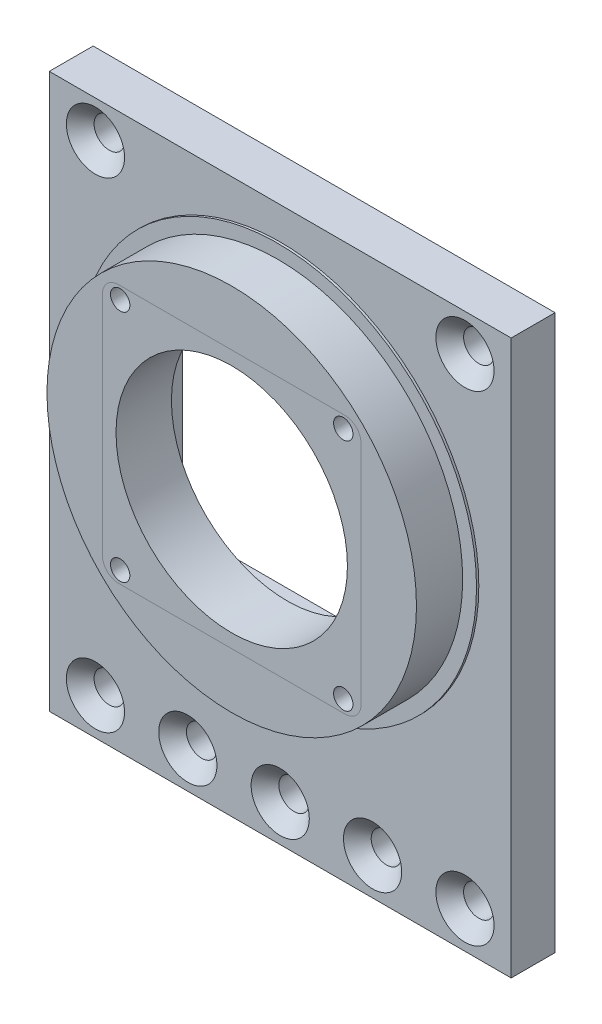
SolidWorks part; units mm, degrees
material "PVC rigide"
ref_plane "Plan de face" through (0, 0, 0) normal (0, 0, 1) x (1, 0, 0)
ref_plane "Plan de dessus" through (0, 0, 0) normal (0, 1, 0) x (1, 0, 0)
ref_plane "Plan de droite" through (0, 0, 0) normal (1, 0, 0) x (0, 0, -1)
sketch "Esquisse1" plane through (0, 0, 0) normal (0, 0, 1) x (1, 0, 0)
  line L1 (28, 28) -> (-28, 28)
  line L2 (28, 28) -> (28, -28)
  line L3 (28, -28) -> (-28, -28)
  line L4 (-28, 28) -> (-28, -28)
  line L5 (28, 28) -> (-28, -28) construction
  line L6 (28, -28) -> (-28, 28) construction
  line L7 (50, 50) -> (-50, 50)
  line L8 (50, 50) -> (50, -50)
  line L9 (50, -50) -> (-50, -50)
  line L10 (-50, 50) -> (-50, -50)
  line L11 (50, 50) -> (-50, -50) construction
  line L12 (50, -50) -> (-50, 50) construction
  circle A0 centre (0, 0) radius 40 construction
  point P0 (0, 0)
  dimension "D2" = 80
  dimension "D1" = 56
  dimension "D3" = 100
extrude "Boss.-Extru.1" add sketch "Esquisse1" along normal blind 10
fillet "Congé1" radius 3.5 4 edges at (-28, -28, 5) (28, 28, 5) (-28, 28, 5) (28, -28, 5)
sketch "Esquisse3" plane through (0, 0, 10) normal (0, 0, 1) x (1, 0, 0)
  line L5 (-28, 24.5) -> (-28, -24.5)
  line L6 (24.5, 28) -> (-24.5, 28)
  line L7 (28, -24.5) -> (28, 24.5)
  line L8 (-24.5, -28) -> (24.5, -28)
  line L9 (-28, 24.5) -> (-28, -24.5)
  line L10 (24.5, 28) -> (-24.5, 28)
  line L11 (28, -24.5) -> (28, 24.5)
  line L12 (-24.5, -28) -> (24.5, -28)
  circle A0 centre (0, 0) radius 40
  arc A5 (-24.5, 28) -> (-28, 24.5) centre (-24.5, 24.5) ccw
  arc A6 (28, 24.5) -> (24.5, 28) centre (24.5, 24.5) ccw
  arc A7 (24.5, -28) -> (28, -24.5) centre (24.5, -24.5) ccw
  arc A8 (-28, -24.5) -> (-24.5, -28) centre (-24.5, -24.5) ccw
  arc A9 (-24.5, 28) -> (-28, 24.5) centre (-24.5, 24.5) ccw
  arc A10 (28, 24.5) -> (24.5, 28) centre (24.5, 24.5) ccw
  arc A11 (24.5, -28) -> (28, -24.5) centre (24.5, -24.5) ccw
  arc A12 (-28, -24.5) -> (-24.5, -28) centre (-24.5, -24.5) ccw
  dimension "D1" = 80
  dimension "D2" = 0
extrude "Boss.-Extru.2" add sketch "Esquisse3" along normal blind 10
sketch "Esquisse4" plane through (0, 0, 10) normal (0, 0, 1) x (1, 0, 0)
  circle A0 centre (0, 0) radius 43
  circle A2 centre (0, 0) radius 40 construction
  dimension "D1" = 3
extrude "Enlèv. mat.-Extru.2" cut sketch "Esquisse4" against normal blind 0.5 flip side to cut
sketch "Esquisse5" plane through (0, 0, 0) normal (0, 0, -1) x (-1, 0, 0)
  line L1 (30.65, -30.65) -> (-30.65, -30.65)
  line L2 (30.65, -30.65) -> (30.65, 30.65)
  line L3 (30.65, 30.65) -> (-30.65, 30.65)
  line L4 (-30.65, -30.65) -> (-30.65, 30.65)
  line L5 (30.65, -30.65) -> (-30.65, 30.65) construction
  line L6 (30.65, 30.65) -> (-30.65, -30.65) construction
  point P0 (0, 0)
  dimension "D1" = 61.3
extrude "Enlèv. mat.-Extru.3" cut sketch "Esquisse5" against normal blind 9
sketch "Esquisse6" plane through (0, 0, 9) normal (0, 0, -1) x (-1, 0, 0)
  line L4 (-30.65, 30.65) -> (-30.65, -30.65)
  line L5 (-30.65, -30.65) -> (30.65, -30.65)
  line L6 (30.65, -30.65) -> (30.65, 30.65)
  line L7 (30.65, 30.65) -> (-30.65, 30.65)
  line L8 (-30.65, 30.65) -> (-30.65, -30.65)
  line L9 (-30.65, -30.65) -> (30.65, -30.65)
  line L10 (30.65, -30.65) -> (30.65, 30.65)
  line L11 (30.65, 30.65) -> (-30.65, 30.65)
  line L13 (28, -24.5) -> (28, 24.5)
  line L14 (-24.5, -28) -> (24.5, -28)
  line L15 (-28, 24.5) -> (-28, -24.5)
  line L16 (24.5, 28) -> (-24.5, 28)
  line L17 (28, -24.5) -> (28, 24.5)
  line L18 (-24.5, -28) -> (24.5, -28)
  line L19 (-28, 24.5) -> (-28, -24.5)
  line L20 (24.5, 28) -> (-24.5, 28)
  arc A4 (28, 24.5) -> (24.5, 28) centre (24.5, 24.5) ccw
  arc A5 (24.5, -28) -> (28, -24.5) centre (24.5, -24.5) ccw
  arc A6 (-28, -24.5) -> (-24.5, -28) centre (-24.5, -24.5) ccw
  arc A7 (-24.5, 28) -> (-28, 24.5) centre (-24.5, 24.5) ccw
  arc A8 (28, 24.5) -> (24.5, 28) centre (24.5, 24.5) ccw
  arc A9 (24.5, -28) -> (28, -24.5) centre (24.5, -24.5) ccw
  arc A10 (-28, -24.5) -> (-24.5, -28) centre (-24.5, -24.5) ccw
  arc A11 (-24.5, 28) -> (-28, 24.5) centre (-24.5, 24.5) ccw
  dimension "D1" = 0
  dimension "D2" = 0
extrude "Boss.-Extru.3" add sketch "Esquisse6" along normal blind 1
sketch "Esquisse12" plane through (0, -50, 0) normal (0, -1, 0) x (1, 0, 0)
  line L4 (50, 9.5) -> (-50, 9.5)
  line L5 (-50, 9.5) -> (-50, 0)
  line L6 (-50, 0) -> (50, 0)
  line L7 (50, 0) -> (50, 9.5)
  line L8 (50, 9.5) -> (-50, 9.5)
  line L9 (-50, 9.5) -> (-50, 0)
  line L10 (-50, 0) -> (50, 0)
  line L11 (50, 0) -> (50, 9.5)
  dimension "D1" = 0
extrude "Boss.-Extru.5" add sketch "Esquisse12" along normal blind 20
sketch "Esquisse7" plane through (0, 0, 8) normal (0, 0, -1) x (-1, 0, 0)
  line L5 (-24.5, -28) -> (24.5, -28)
  line L6 (28, -24.5) -> (28, 24.5)
  line L7 (24.5, 28) -> (-24.5, 28)
  line L8 (-28, 24.5) -> (-28, -24.5)
  line L9 (-24.5, -28) -> (24.5, -28)
  line L10 (28, -24.5) -> (28, 24.5)
  line L11 (24.5, 28) -> (-24.5, 28)
  line L12 (-28, 24.5) -> (-28, -24.5)
  circle A0 centre (0, 0) radius 25.05
  arc A5 (24.5, -28) -> (28, -24.5) centre (24.5, -24.5) ccw
  arc A6 (28, 24.5) -> (24.5, 28) centre (24.5, 24.5) ccw
  arc A7 (-24.5, 28) -> (-28, 24.5) centre (-24.5, 24.5) ccw
  arc A8 (-28, -24.5) -> (-24.5, -28) centre (-24.5, -24.5) ccw
  arc A9 (24.5, -28) -> (28, -24.5) centre (24.5, -24.5) ccw
  arc A10 (28, 24.5) -> (24.5, 28) centre (24.5, 24.5) ccw
  arc A11 (-24.5, 28) -> (-28, 24.5) centre (-24.5, 24.5) ccw
  arc A12 (-28, -24.5) -> (-24.5, -28) centre (-24.5, -24.5) ccw
  dimension "D1" = 50.1
  dimension "D2" = 0
extrude "Boss.-Extru.4" add sketch "Esquisse7" against normal up to surface (12 mm away) up to face at (40, 0, 20)
sketch "Esquisse10" plane through (0, 0, 8) normal (0, 0, -1) x (-1, 0, 0)
  line L1 (-24.1504, -25.3329) -> (24.1504, -25.3329) construction
  line L2 (-24.1504, -25.3329) -> (-24.1504, 25.3329) construction
  line L3 (-24.1504, 25.3329) -> (24.1504, 25.3329) construction
  line L4 (24.1504, -25.3329) -> (24.1504, 25.3329) construction
  line L5 (-24.1504, -25.3329) -> (24.1504, 25.3329) construction
  line L6 (-24.1504, 25.3329) -> (24.1504, -25.3329) construction
  circle A0 centre (0, 0) radius 35 construction
  point P0 (0, 0)
  dimension "D1" = 70
hole_wizard "Trou taraudé M5x0.81" positions "Esquisse3D2" profile "Esquisse11" tap size "M5x0.8" standard "Ansi Metric" end condition through all
sketch3d "Esquisse3D2"
  point P0 (24.1504, 25.3329, 8)
  point P3 (24.1504, -25.3329, 8)
  point P6 (-24.1504, 25.3329, 8)
  point P9 (-24.1504, -25.3329, 8)
sketch "Esquisse11" plane through (24.1504, 25.3329, 8) normal (1, 0, 0) x (0, 1, 0)
  line L0 (0, 0) -> (0, 12)
  line L1 (0, 12) -> (2.1, 12)
  line L2 (2.1, 12) -> (2.1, 0)
  line L5 (2.1, 0) -> (0, 0)
  line L11 (0, -6.35) -> (0, 107.95) construction
  dimension "Diamètre principal du filetage" = 4.2
  dimension "Profondeur du trou pour taraudage jusqu'au prochain" = 12
sketch "Esquisse13" plane through (0, 0, 9.5) normal (0, 0, 1) x (1, 0, 0)
  line L0 (-50, -62) -> (50, -62) construction
  line L1 (-50, 50) -> (-50, -70) construction
  line L2 (50, -70) -> (50, 50) construction
  line L3 (50, -70) -> (-50, -70) construction
  line L4 (0, -62) -> (0, -70) construction
  line L5 (-40, -62) -> (-40, -70) construction
  line L6 (40, -62) -> (40, -70) construction
  line L7 (-20, -62) -> (-20, -70) construction
  line L8 (20, -62) -> (20, -70) construction
  line L9 (-50, 42) -> (50, 42) construction
  line L10 (50, 50) -> (-50, 50) construction
  line L11 (-40, -62) -> (-40, 50) construction
  line L12 (40, -62) -> (40, 50) construction
  dimension "D1" = 8
  dimension "D2" = 10
  dimension "D3" = 20
  dimension "D4" = 8
hole_wizard "Fraisage pour vis à tête fraisée M61" positions "Esquisse3D3" profile "Esquisse14" countersink size "M6" standard "Ansi Metric" end condition through all
sketch3d "Esquisse3D3"
  line L0 (-40, -62, 9.5) -> (-40, -70, 9.5) construction
  line L1 (-50, 42, 9.5) -> (50, 42, 9.5) construction
  line L2 (40, -62, 9.5) -> (40, 50, 9.5) construction
  line L3 (-40, -62, 9.5) -> (-40, 50, 9.5) construction
  point P0 (-40, -62, 9.5)
  point P4 (-20, -62, 9.5)
  point P7 (0, -62, 9.5)
  point P10 (20, -62, 9.5)
  point P13 (40, -62, 9.5)
  point P21 (-40, 42, 9.5)
  point P25 (40, 42, 9.5)
sketch "Esquisse14" plane through (-40, -62, 9.5) normal (1, 0, 0) x (0, -1, 0)
  line L0 (0, 0) -> (0, 9.5)
  line L1 (0, 9.5) -> (3.3, 9.5)
  line L2 (3.3, 9.5) -> (3.3, 3)
  line L3 (3.3, 3) -> (6.3, 0)
  line L5 (6.3, 0) -> (0, 0)
  line L6 (-3.3, 3) -> (-6.3, 0) construction
  line L11 (0, -6.35) -> (0, 107.95) construction
  dimension "Diamètre du perçage jusqu'au prochain" = 6.6
  dimension "Profondeur du perçage jusqu'au prochain" = 9.5
  dimension "Diamètre du fraisage entrant" = 12.6
  dimension "Angle du fraisage entrant" = 90
fillet "Congé2" radius 4 4 edges at (-30.65, 30.65, 4) (-30.65, -30.65, 4) (30.65, 30.65, 4) (30.65, -30.65, 4)
